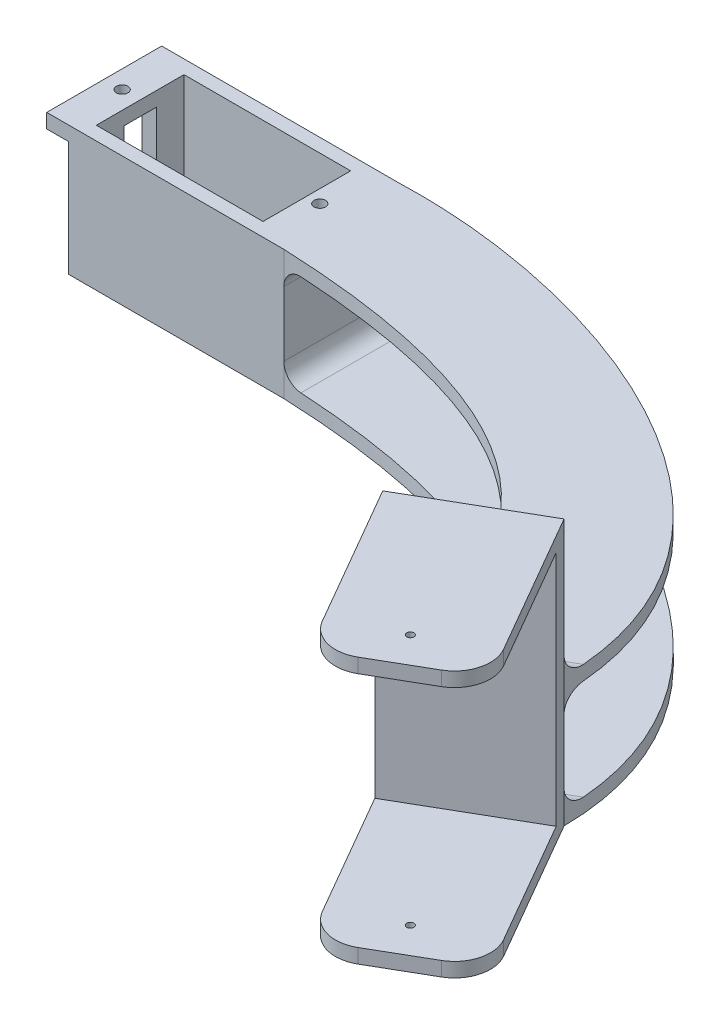
SolidWorks part; units mm, degrees
material "ABS"
ref_plane "Front Plane" through (0, 0, 0) normal (0, 0, 1) x (1, 0, 0)
ref_plane "Top Plane" through (0, 0, 0) normal (0, 1, 0) x (1, 0, 0)
ref_plane "Right Plane" through (0, 0, 0) normal (1, 0, 0) x (0, 0, -1)
sketch "Sketch1" plane through (0, 0, 0) normal (0, 1, 0) x (1, 0, 0)
  line L1 (15, -8) -> (-15, -8)
  line L2 (15, -8) -> (15, 8)
  line L3 (15, 8) -> (-15, 8)
  line L4 (-15, -8) -> (-15, 8)
  line L5 (15, -8) -> (-15, 8) construction
  line L6 (15, 8) -> (-15, -8) construction
  point P0 (0, 0)
  dimension "D1" = 30
  dimension "D2" = 16
extrude "Boss-Extrude1" add sketch "Sketch1" along normal blind 2
sketch "Sketch2" plane through (0, 2, 0) normal (0, 1, 0) x (1, 0, 0)
  line L0 (-1000, 0) -> (49000, 0) construction
  line L1 (-15, -8) -> (15, -8) construction
  line L2 (-15, 8) -> (-13, 8)
  line L3 (-15, 8) -> (-15, -8)
  line L4 (-15, -8) -> (-13, -8)
  line L5 (-13, 6.1) -> (-13, -6.1)
  line L6 (-13, -8) -> (10.2, -8)
  line L7 (-13, 8) -> (10.2, 8)
  line L9 (-13, 6.1) -> (10.2, 6.1)
  line L12 (-13, -6.1) -> (10.2, -6.1)
  line L13 (10.2, 8) -> (15, 8)
  line L14 (10.2, 6.1) -> (10.2, -6.1)
  line L15 (10.2, -8) -> (15, -8)
  line L16 (15, 8) -> (15, -8)
  dimension "D1" = 2
  dimension "D2" = 1.9
  dimension "D3" = 23.2
  dimension "D4" = 4.8
  dimension "D5" = 2
  dimension "D6" = 12.2
extrude "Boss-Extrude2" add sketch "Sketch2" along normal blind 16
sketch "Sketch3" plane through (-13, 0, 0) normal (1, 0, 0) x (0, 0, -1)
  line L0 (0, -1000) -> (0, 49000) construction
  line L1 (8, 0) -> (-8, 0) construction
  line L2 (2.25, 18) -> (-2.25, 18)
  line L3 (2.25, 18) -> (2.25, 5)
  line L4 (2.25, 5) -> (-2.25, 5)
  line L5 (-2.25, 18) -> (-2.25, 5)
  line L6 (2.25, 18) -> (-2.25, 5) construction
  line L7 (2.25, 5) -> (-2.25, 18) construction
  line L8 (8, 18) -> (-8, 18) construction
  point P1 (0, 11.5)
  dimension "D1" = 5
  dimension "D2" = 13
  dimension "D3" = 4.5
extrude "Cut-Extrude1" cut sketch "Sketch3" against normal up to next
sketch "Sketch8" plane through (0, 0, 0) normal (0, -1, 0) x (1, 0, 0)
  line L0 (-1000, 0) -> (49000, 0) construction
  line L1 (-15, -8) -> (-15, 8) construction
  circle A0 centre (-10, 0) radius 0.8
  dimension "D1" = 1.6
  dimension "D2" = 5
extrude "Cut-Extrude3" cut sketch "Sketch8" against normal blind 2
sketch "Sketch9" plane through (0, 18, 0) normal (0, 1, 0) x (1, 0, 0)
  line L0 (15, 8) -> (-15, 8) construction
  line L1 (-13, 8) -> (-18, 8)
  line L2 (-13, 8) -> (-13, -8)
  line L3 (-13, -8) -> (-18, -8)
  line L4 (-18, 8) -> (-18, -8)
  line L5 (-13, 6.1) -> (-13, 2.25) construction
  line L6 (0, -1000) -> (0, 49000) construction
  line L7 (10.2, -6.1) -> (10.2, 6.1) construction
  line L8 (10.2, 8) -> (14.2, 8)
  line L9 (10.2, 8) -> (10.2, -8)
  line L10 (10.2, -8) -> (14.2, -8)
  line L11 (14.2, 8) -> (14.2, -8)
  dimension "D1" = 5
  dimension "D2" = 16
  dimension "D3" = 4
  dimension "D4" = 16
extrude "Boss-Extrude4" add sketch "Sketch9" against normal blind 2
sketch "Sketch10" plane through (0, 18, 0) normal (0, 1, 0) x (1, 0, 0)
  line L0 (-1000, 0) -> (49000, 0) construction
  line L1 (10.2, -6.1) -> (10.2, 6.1) construction
  line L2 (-13, 6.1) -> (-13, -6.1) construction
  circle A0 centre (12, 0) radius 0.8
  circle A1 centre (-15.501, 0) radius 0.8
  dimension "D1" = 1.6
  dimension "D3" = 1.6
  dimension "D2" = 1.8
  dimension "D4" = 2.501
extrude "Cut-Extrude4" cut sketch "Sketch10" against normal blind 5
sketch "Sketch12" plane through (0, 0, 0) normal (0, 1, 0) x (1, 0, 0)
  line L0 (-15, -8) -> (15, -8) construction
  line L2 (70, -1000) -> (70, 49000) construction
  line L3 (-930, -40) -> (49070, -40) construction
  line L4 (86, -1000) -> (86, 49000) construction
  line L5 (-779.9511, -539.9571) -> (42521.3191, 24460.0429) construction
  line L6 (70, -49.2376) -> (86, -40)
  line L7 (15, -8) -> (15, 8) construction
  line L8 (15, 8) -> (15, -8)
  spline S0 degree 2 poles (15, -8) (69.8863, -10.2488) (70, -49.2376) knots 0 0 0 1 1 1
  spline S1 degree 3 poles (15, 8) (44.0192, 9.0553) (85.7373, -7.1634) (86, -40) knots 0 0 0 0 1 1 1 1
  dimension "D1" = 55
  dimension "D2" = 16
  dimension "D3" = 32
  dimension "D4" = 30
extrude "Boss-Extrude6" add sketch "Sketch12" along normal blind 2
sketch "Sketch14" plane through (38.8205, 0, 67.2391) normal (0.5, 0, 0.866) x (0.866, 0, -0.5)
  line L0 (54.4782, 2) -> (54.4782, 0) construction
  line L1 (36.003, 0) -> (54.4782, 0)
  line L2 (36.003, 0) -> (36.003, 37)
  line L3 (36.003, 37) -> (54.4782, 37)
  line L4 (54.4782, 0) -> (54.4782, 37)
  dimension "D1" = 37
extrude "Boss-Extrude7" add sketch "Sketch14" along normal blind 3
sketch "Sketch15" plane through (40.3205, 0, 69.8372) normal (0.5, 0, 0.866) x (0.866, 0, -0.5)
  line L0 (54.4782, 0) -> (54.4782, 37) construction
  line L1 (36.003, 0) -> (54.4782, 0)
  line L2 (36.003, 0) -> (36.003, 2)
  line L3 (36.003, 2) -> (54.4782, 2)
  line L4 (54.4782, 0) -> (54.4782, 2)
  line L6 (36.003, 37) -> (54.4782, 37)
  line L7 (36.003, 37) -> (36.003, 35)
  line L8 (36.003, 35) -> (54.4782, 35)
  line L9 (54.4782, 37) -> (54.4782, 35)
  dimension "D1" = 2
  dimension "D2" = 2
extrude "Boss-Extrude8" add sketch "Sketch15" along normal blind 25
pattern_linear "LPattern1" count 2 spacing 16 along (0, 1, 0) of "Boss-Extrude6"
fillet "Fillet2" radius 2.5 5 edges at (15, 2, 0) (78, 16, 44.6188) (78, 18, 44.6188)
fillet "Fillet3" radius 5 4 edges at (100, 36, 64.2487) (84, 36, 73.4863) (100, 1, 64.2487) (84, 1, 73.4863)
sketch "Sketch16" plane through (0, 0, 0) normal (0, -1, 0) x (1, 0, 0)
  line L0 (97.5, 59.9186) -> (87.5, 42.5981) construction
  line L1 (88.3301, 70.9863) -> (95.6699, 66.7487) construction
  circle A0 centre (89.2728, 64.6686) radius 0.5
  dimension "D1" = 5
  dimension "D3" = 1
  dimension "D2" = 9.5
extrude "Cut-Extrude6" cut sketch "Sketch16" against normal through all both and the other way through all
